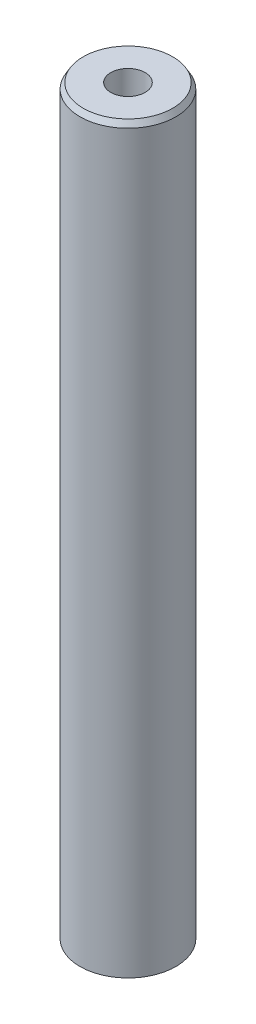
SolidWorks part; units mm, degrees
ref_plane "Front Plane" through (0, 0, 0) normal (0, 0, 1) x (1, 0, 0)
ref_plane "Top Plane" through (0, 0, 0) normal (0, 1, 0) x (1, 0, 0)
ref_plane "Right Plane" through (0, 0, 0) normal (1, 0, 0) x (0, 0, -1)
sketch "Sketch1" plane through (0, 0, 0) normal (0, 1, 0) x (1, 0, 0)
  circle A0 centre (0, 0) radius 32.5
  dimension "SHAFT_OD" = 65
extrude "Boss-Extrude1" add sketch "Sketch1" along normal blind 504.307
sketch "Sketch2" plane through (0, 0, 0) normal (0, 1, 0) x (1, 0, 0)
  circle A0 centre (0, 0) radius 11.6462
  dimension "BORE_D" = 23.2924
extrude "Cut-Extrude1" cut sketch "Sketch2" along normal through all
chamfer "Chamfer1" distance 3.8657 angle 30.111 2 edges at (0, 504.307, 32.5) (0, 0, 32.5) first distance on face at (0, 504.307, 32.5) first distance on face at (0, 0, 11.6462)
